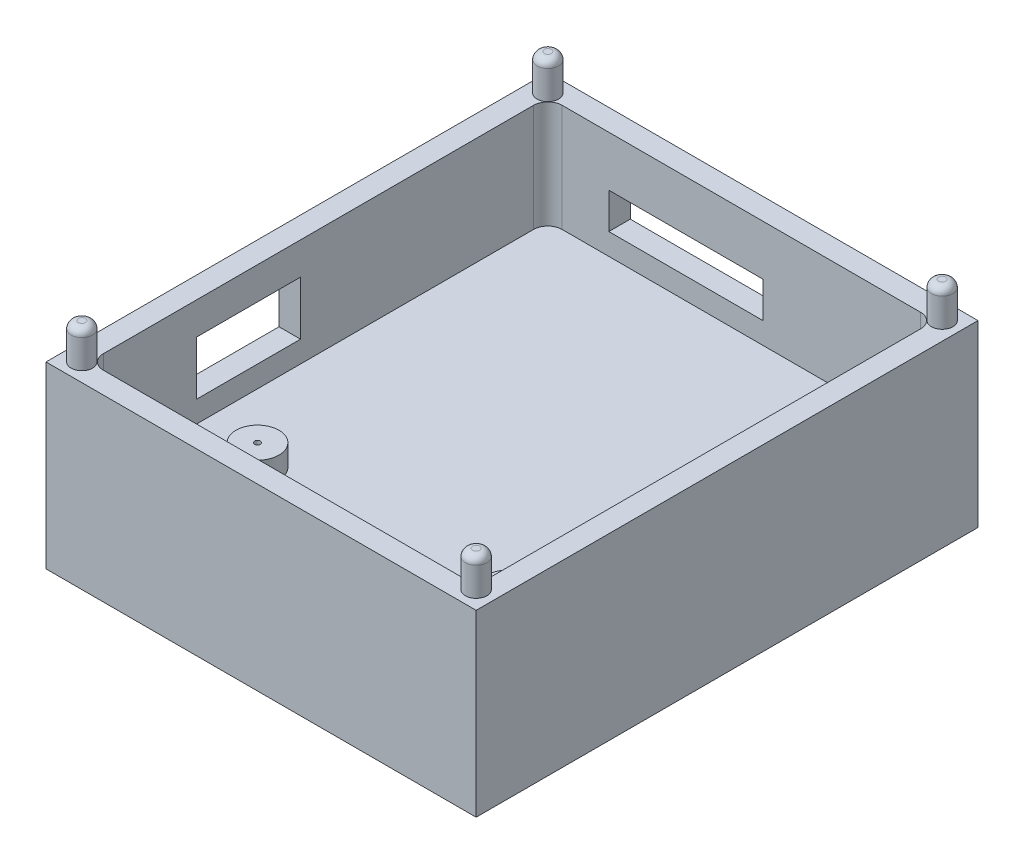
SolidWorks part; units mm, degrees
ref_plane "Front Plane" through (0, 0, 0) normal (0, 0, 1) x (1, 0, 0)
ref_plane "Top Plane" through (0, 0, 0) normal (0, 1, 0) x (1, 0, 0)
ref_plane "Right Plane" through (0, 0, 0) normal (1, 0, 0) x (0, 0, -1)
sketch "Sketch1" plane through (0, 0, 0) normal (0, 1, 0) x (1, 0, 0)
  line L0 (-25.8779, 33.7023) -> (-25.8779, -36.2977)
  line L1 (-25.8779, -36.2977) -> (34.1221, -36.2977)
  line L2 (34.1221, -36.2977) -> (34.1221, 33.7023)
  line L3 (34.1221, 33.7023) -> (-25.8779, 33.7023)
  dimension "D1" = 60
  dimension "D2" = 70
extrude "Boss-Extrude1" add sketch "Sketch1" along normal blind 10
sketch "Sketch2" plane through (0, 10, 0) normal (0, 1, 0) x (1, 0, 0)
  line L0 (-22.8779, 30.7023) -> (-22.8779, -33.2977)
  line L1 (-22.8779, -33.2977) -> (31.1221, -33.2977)
  line L2 (31.1221, -33.2977) -> (31.1221, 30.7023)
  line L3 (31.1221, 30.7023) -> (-22.8779, 30.7023)
  line L4 (-25.8779, 33.7023) -> (-25.8779, -36.2977) construction
  line L5 (-25.8779, -36.2977) -> (34.1221, -36.2977) construction
  line L6 (34.1221, -36.2977) -> (34.1221, 33.7023) construction
  line L7 (34.1221, 33.7023) -> (-25.8779, 33.7023) construction
  line L8 (-25.8779, 33.7023) -> (-25.8779, -36.2977)
  line L9 (-25.8779, -36.2977) -> (34.1221, -36.2977)
  line L10 (34.1221, -36.2977) -> (34.1221, 33.7023)
  line L11 (34.1221, 33.7023) -> (-25.8779, 33.7023)
  dimension "D1" = 3
  dimension "D2" = 3
  dimension "D3" = 3
  dimension "D4" = 3
extrude "Boss-Extrude2" add sketch "Sketch2" along normal blind 15
sketch "Sketch3" plane through (0, 25, 0) normal (0, 1, 0) x (1, 0, 0)
  line L0 (34.1221, 33.7023) -> (-25.8779, 33.7023) construction
  line L1 (-25.8779, 33.7023) -> (-25.8779, -36.2977) construction
  line L2 (34.1221, -36.2977) -> (34.1221, 33.7023) construction
  line L3 (-25.8779, -36.2977) -> (34.1221, -36.2977) construction
  circle A0 centre (-23.3779, 31.2023) radius 1.5
  circle A1 centre (31.6221, 31.2023) radius 1.5
  circle A2 centre (31.6221, -33.7977) radius 1.5
  circle A3 centre (-23.3779, -33.7977) radius 1.5
  dimension "D2" = 3
  dimension "D4" = 3
  dimension "D7" = 3
  dimension "D10" = 3
  dimension "D1" = 2.5
  dimension "D3" = 2.5
  dimension "D5" = 2.5
  dimension "D6" = 2.5
  dimension "D8" = 2.5
  dimension "D9" = 2.5
  dimension "D11" = 2.5
  dimension "D12" = 2.5
extrude "Boss-Extrude3" add sketch "Sketch3" along normal blind 5
sketch "Sketch8" plane through (0, 10, 0) normal (0, 1, 0) x (1, 0, 0)
  line L2 (31.1221, 30.7023) -> (-22.8779, 30.7023) construction
  line L6 (31.1221, -32.3835) -> (31.1221, 29.7881) construction
  circle A0 centre (21.6221, -19.2977) radius 3
  circle A1 centre (21.6221, -19.2977) radius 0.4
  circle A2 centre (-13.3779, -19.2977) radius 3
  circle A3 centre (-13.3779, -19.2977) radius 0.4
  circle A4 centre (23.6221, 25.7023) radius 3
  circle A5 centre (23.6221, 25.7023) radius 0.4
  dimension "D1" = 0.8
  dimension "D2" = 6
  dimension "D9" = 6
  dimension "D10" = 0.8
  dimension "D11" = 0.8
  dimension "D12" = 6
  dimension "D3" = 45
  dimension "D4" = 35
  dimension "D5" = 0
  dimension "D6" = 5
  dimension "D7" = 7.5
extrude "Boss-Extrude4" add sketch "Sketch8" along normal blind 3
sketch "Sketch11" plane through (0, 10, 0) normal (0, 1, 0) x (1, 0, 0)
  circle A0 centre (-13.3779, -19.2977) radius 0.4
  circle A1 centre (21.6221, -19.2977) radius 0.4
  circle A2 centre (23.6221, 25.7023) radius 0.4
  dimension "D1" = 0.8
  dimension "D2" = 0.8
  dimension "D3" = 0.8
extrude "Cut-Extrude1" cut sketch "Sketch11" against normal blind 4
sketch "Sketch12" plane through (0, 0, -33.7023) normal (0, 0, -1) x (-1, 0, 0)
  line L1 (-7.1221, 18) -> (14.3779, 18)
  line L2 (-7.1221, 18) -> (-7.1221, 13)
  line L3 (-7.1221, 13) -> (14.3779, 13)
  line L4 (14.3779, 18) -> (14.3779, 13)
  line L5 (25.8779, 25) -> (25.8779, 0) construction
  line L6 (-34.1221, 0) -> (25.8779, 0) construction
  dimension "D1" = 5
  dimension "D2" = 21.5
  dimension "D3" = 13
  dimension "D4" = 11.5
extrude "Cut-Extrude2" cut sketch "Sketch12" against normal blind 5
sketch "Sketch13" plane through (34.1221, 0, 0) normal (1, 0, 0) x (0, 0, -1)
  line L1 (-14.2977, 13) -> (-1.7977, 13)
  line L2 (-14.2977, 13) -> (-14.2977, 20.5)
  line L3 (-14.2977, 20.5) -> (-1.7977, 20.5)
  line L4 (-1.7977, 13) -> (-1.7977, 20.5)
  line L7 (-36.2977, 0) -> (33.7023, 0) construction
  dimension "D1" = 12.5
  dimension "D2" = 7.5
  dimension "D3" = 13
  dimension "D4" = 8
sketch "Sketch15" plane through (0, 0, 0) normal (0, -1, 0) x (1, 0, 0)
  line L2 (-25.8779, -33.7023) -> (-25.8779, 36.2977) construction
  line L3 (-25.8779, 36.2977) -> (34.1221, 36.2977) construction
  line L4 (34.1221, -33.7023) -> (-25.8779, -33.7023) construction
  circle A0 centre (4.1221, 1.2977) radius 6
  circle A1 centre (4.1221, 1.2977) radius 1.25
  circle A2 centre (4.1221, 23.7977) radius 6
  circle A3 centre (4.1221, 23.7977) radius 1.25
  circle A4 centre (4.1221, -21.2023) radius 6
  circle A5 centre (4.1221, -21.2023) radius 1.25
  dimension "D1" = 12
  dimension "D2" = 2.5
  dimension "D3" = 12
  dimension "D4" = 2.5
  dimension "D5" = 12
  dimension "D6" = 2.5
  dimension "D7" = 30
  dimension "D8" = 35
  dimension "D9" = 30
  dimension "D10" = 12.5
  dimension "D11" = 11.25
  dimension "D12" = 30
fillet "Fillet2" radius 1 4 edges at (31.6221, 30, 35.2977) (-23.3779, 30, 35.2977) (-23.3779, 30, -29.7023) (31.6221, 30, -29.7023)
sketch "Sketch18" plane through (0, 0, 0) normal (0, -1, 0) x (1, 0, 0)
  line L0 (-25.8779, 36.2977) -> (34.1221, 36.2977) construction
  circle A0 centre (4.1221, 23.7977) radius 1.25
  circle A1 centre (4.1221, 1.2977) radius 1.25
  circle A2 centre (4.1221, -21.2023) radius 1.25
  dimension "D2" = 2.5
  dimension "D4" = 2.5
  dimension "D5" = 2.5
  dimension "D1" = 12.5
  dimension "D3" = 35
extrude "Cut-Extrude6" cut sketch "Sketch18" against normal blind 7
sketch "Sketch20" plane through (-25.8779, 0, 0) normal (-1, 0, 0) x (0, 0, 1)
  line L0 (3.7977, 13) -> (18.2977, 13)
  line L1 (3.7977, 13) -> (3.7977, 20.5)
  line L2 (3.7977, 20.5) -> (18.2977, 20.5)
  line L3 (18.2977, 13) -> (18.2977, 20.5)
  line L4 (-33.7023, 0) -> (36.2977, 0) construction
  dimension "D1" = 14.5
  dimension "D2" = 7.5
  dimension "D3" = 13
  dimension "D4" = 4
extrude "Cut-Extrude7" cut sketch "Sketch20" against normal blind 7
fillet "Fillet3" radius 2 4 edges at (31.1221, 17.5, 33.2977) (31.1221, 17.5, -30.7023) (-22.8779, 17.5, -30.7023) (-22.8779, 17.5, 33.2977)
